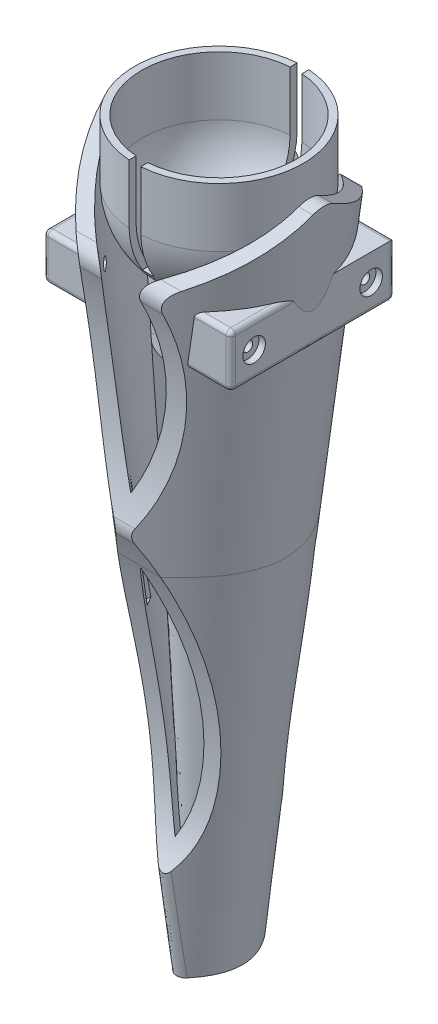
SolidWorks part; units mm, degrees
material "CRPS"
ref_plane "Front Plane" through (0, 0, 0) normal (0, 0, 1) x (1, 0, 0)
ref_plane "Top Plane" through (0, 0, 0) normal (0, 1, 0) x (1, 0, 0)
ref_plane "Right Plane" through (0, 0, 0) normal (1, 0, 0) x (0, 0, -1)
ref_plane "Plane1" through (0, 381, 0) normal (0, 1, 0) x (1, 0, 0)
sketch "Sketch1" plane through (0, 0, 0) normal (0, 1, 0) x (1, 0, 0)
  line L0 (0, 25.4) -> (0, -25.4) construction
  line L1 (-24.0706, 0) -> (20.9677, 0) construction
  ellipse E0 centre (0, 0) end of major axis (0, -25.4) minor radius 12.7 construction
  spline S0 degree 2 poles (0, 25.4) (-25.4, 0) (0, -25.4) knots 0 0 0 1 1 1
  spline S1 degree 2 poles (0, 25.4) (25.4, 0) (0, -25.4) knots 0 0 0 1 1 1
  dimension "D1" = 50.8
  dimension "D2" = 25.4
  dimension "D3" = 25.4
sketch "Sketch2" plane through (0, 381, 0) normal (0, 1, 0) x (1, 0, 0)
  line L0 (0, 76.2) -> (0, -76.2) construction
  line L1 (-84.7486, 0) -> (88.0794, 0) construction
  spline S0 degree 2 poles (0, 76.2) (-114.3, 0) (0, -76.2) knots 0 0 0 1 1 1
  spline S4 degree 2 poles (0, 76.2) (114.3, 0) (0, -76.2) knots 0 0 0 1 1 1
  dimension "D1" = 152.4
loft "Loft1" add profiles "Sketch2", "Sketch1" connector at (0, 381, -76.2) connector at (0, 0, -25.4)
shell "Shell1" thickness 7.62 removed face at (0, 381, 0)
sketch "Sketch3" plane through (0, 0, 0) normal (1, 0, 0) x (0, 0, -1)
  line L0 (0, -10.6087) -> (0, 387.8893) construction
  line L5 (0, 459.1301) -> (-203.7464, 459.1301)
  line L6 (-203.7464, 459.1301) -> (-203.7464, 12.9064)
  line L7 (-203.7464, 12.9064) -> (-69.702, 12.9064)
  line L8 (-69.702, 12.9064) -> (-69.702, 27.0618)
  line L10 (0, 380.3715) -> (0, 459.1301)
  line L11 (-76.2, 381) -> (-25.4, 0) construction
  line L13 (0, 380.3715) -> (-55.9194, 344.4077)
  arc A2 (-55.9194, 344.4077) -> (-52.7686, 223.1491) centre (-207.8896, 279.7886) cw
  spline S0 degree 3 poles (-52.7686, 223.1491) (-29.0646, 178.2411) (18.4946, 46.1783) (-69.702, 27.0618) knots 0 0 0 0 1 1 1 1
extrude "Cut-Extrude3" cut sketch "Sketch3" against normal through all both and the other way through all
mirror "Mirror1" about plane through (0, 0, 0) normal (0, 0, 1) of "Cut-Extrude3"
sketch "Sketch4" plane through (0, 0, 0) normal (0, 0, 1) x (1, 0, 0)
  line L0 (0, 446.903) -> (0, 0) construction
  line L1 (49.405, 380.3715) -> (0, 380.3715) construction
  line L7 (0, 380.3715) -> (0, 393.0715)
  line L8 (0, 393.0715) -> (45.72, 393.0715)
  line L9 (45.72, 393.0715) -> (45.72, 361.0934)
  line L10 (0, 380.3715) -> (0, 316.8715)
  arc A1 (0, 316.8715) -> (45.72, 361.0934) centre (0.1911, 362.4193) ccw
  spline S1 degree 3 poles (20.373, 344.4077) (25.1314, 346.8179) (29.623, 349.3373) (35.8389, 353.3301) (37.8235, 354.6968) (41.5893, 357.5136) (43.3706, 358.9636) (46.6928, 361.9622) (48.2339, 363.5106) (49.9789, 365.5205) (50.3189, 365.9264) (50.9751, 366.7401) (51.9255, 367.9653) (52.7722, 369.2049) (55.3558, 373.3704) (56.661, 376.8089) (57.0767, 380.3715) knots 0 0 0 0 0.25 0.25 0.375 0.375 0.5 0.5 0.625 0.625 0.65625 0.65625 0.6875 0.75 0.75 1 1 1 1 construction
  dimension "D1" = 12.7
  dimension "D2" = 63.5
  dimension "D3" = 45.72
revolve "Revolve1" add sketch "Sketch4" angle 360 about L0
ref_plane "Plane2" through (0, 342.9, 0) normal (0, 1, 0) x (1, 0, 0)
sketch "Sketch7" plane through (0, 342.9, 0) normal (0, 1, 0) x (1, 0, 0)
  circle A0 centre (0, 0) radius 28.575
  dimension "D1" = 57.15
sketch "Sketch9" plane through (0, 7.62, 0) normal (0, 1, 0) x (1, 0, 0)
  circle A1 centre (0, 0) radius 12.7
  dimension "D1" = 25.4
sketch "Sketch11" plane through (0, 0, 0) normal (0, 0, 1) x (1, 0, 0)
  line L0 (0, 0) -> (0, 452.1769) construction
  line L10 (-41.91, 393.0715) -> (-41.91, 361.0934)
  line L11 (45.72, 393.0715) -> (-45.72, 393.0715) construction
  line L12 (45.72, 361.0934) -> (-45.72, 361.0934) construction
  line L13 (0, 319.9717) -> (0, 393.0715)
  line L14 (0, 393.0715) -> (-41.91, 393.0715)
  arc A2 (-41.91, 361.0934) -> (0, 319.9717) centre (0.1848, 362.0776) ccw
  dimension "D1" = 41.91
sketch "Sketch12" plane through (0, 0, 0) normal (1, 0, 0) x (0, 0, -1)
  line L0 (0, 0) -> (0, 403.0292) construction
  line L8 (-4.171, 269.2418) -> (-4.171, 173.919)
  line L10 (-33.8119, 288.677) -> (-25.8319, 168.9729)
  arc A7 (-33.8119, 288.677) -> (-4.171, 269.2418) centre (-28.7091, 264.1389) cw
  arc A8 (-4.171, 173.919) -> (-25.8319, 168.9729) centre (-17.4745, 182.2764) cw
ref_plane "Plane3" through (50.8, 0, 0) normal (1, 0, 0) x (0, 0, -1)
sketch "Sketch13" plane through (50.8, 0, 0) normal (1, 0, 0) x (0, 0, -1)
  line L0 (0, 0) -> (0, 407.2777) construction
  line L2 (-44.45, 338.1582) -> (44.45, 338.1582)
  line L3 (-44.45, 338.1582) -> (-44.45, 309.5418)
  line L4 (-44.45, 309.5418) -> (44.45, 309.5418)
  line L5 (44.45, 338.1582) -> (44.45, 309.5418)
  line L6 (-44.45, 338.1582) -> (44.45, 309.5418) construction
  line L7 (-44.45, 309.5418) -> (44.45, 338.1582) construction
  point P3 (0, 323.85)
  dimension "D1" = 323.85
  dimension "D2" = 88.9
extrude "Boss-Extrude2" add sketch "Sketch13" against normal up to surface (19.3871 mm away) up to face at (20.0933, 168.816, 3.5644)
ref_plane "Plane4" through (-50.8, 0, 0) normal (1, 0, 0) x (0, 0, -1)
sketch "Sketch14" plane through (-50.8, 0, 0) normal (1, 0, 0) x (0, 0, -1)
  line L0 (-23.876, 338.1582) -> (-23.876, 311.423) construction
  line L5 (-44.45, 336.277) -> (44.45, 336.277)
  line L6 (-44.45, 336.277) -> (-44.45, 311.423)
  line L7 (-44.45, 311.423) -> (44.45, 311.423)
  line L8 (44.45, 336.277) -> (44.45, 311.423)
  line L9 (-44.45, 336.277) -> (44.45, 311.423) construction
  line L10 (-44.45, 311.423) -> (44.45, 336.277) construction
  line L11 (-44.45, 338.1582) -> (44.45, 338.1582) construction
  line L12 (-23.876, 323.85) -> (-44.45, 323.85) construction
  line L13 (0, 345.8944) -> (0, 299.4688) construction
  line L14 (0, 0) -> (0, 407.2777) construction
  point P0 (0, 323.85)
  dimension "D1" = 88.9
  dimension "D2" = 323.85
extrude "Boss-Extrude4" add sketch "Sketch14" along normal up to surface (19.6671 mm away) up to face at (-21.1882, 173.8157, -2.0801)
fillet "Fillet2" radius 2.54 17 edges at (38.9583, 309.5418, 44.45) (41.1065, 338.1582, 44.45) (50.8, 323.85, 44.45) (50.8, 338.1582, 27.8992) (50.8, 309.5418, 0) (38.9583, 309.5418, -44.45) (41.1065, 338.1582, -44.45) (50.8, 323.85, -44.45) (-40.9665, 336.277, 44.45) (-39.1008, 311.423, 44.45) (-50.8, 323.85, 44.45) (-50.8, 311.423, 0) (-50.8, 336.277, 27.4106) (-39.1008, 311.423, -44.45) (-50.8, 323.85, -44.45) (-40.9665, 336.277, -44.45) (-50.8, 336.277, -27.4106)
sketch "Sketch28" plane through (0, 0, 0) normal (0, 0, 1) x (1, 0, 0)
  line L0 (0, 0) -> (0, 423.247) construction
  line L7 (-3.175, 414.0584) -> (3.175, 414.0584)
  line L8 (-3.175, 414.0584) -> (-3.175, 337.8584)
  line L9 (-3.175, 337.8584) -> (3.175, 337.8584)
  line L10 (3.175, 414.0584) -> (3.175, 337.8584)
  dimension "D1" = 6.35
  dimension "D2" = 76.2
loft "Loft2" add profiles "Sketch7", "Sketch9" connector at (0, 342.9, 28.575) connector at (0, 7.62, 12.7)
revolve "Cut-Revolve2" cut sketch "Sketch11" angle 360 about L0
extrude "Cut-Extrude6" cut sketch "Sketch12" against normal mid plane 36.83
mirror "Mirror2" about plane through (0, 0, 0) normal (0, 0, 1) of "Cut-Extrude6" second plane through (0, 0, 0) second plane normal (1, 0, 0)
extrude "Cut-Extrude7" cut sketch "Sketch28" against normal through all both and the other way through all
fillet "Fillet3" radius 10 8 edges at (53.2408, 380.3715, 0) (14.3124, 344.4077, 55.9194) (0, 223.1491, 52.7686) (-53.2408, 380.3715, 0) (14.3124, 344.4077, -55.9194) (-14.3124, 344.4077, -55.9194) (0, 223.1491, -52.7686) (-14.3124, 344.4077, 55.9194)
fillet "Fillet4" radius 5.08 2 edges
sketch "Sketch34" plane through (0, 0, 0) normal (0, -1, 0) x (1, 0, 0)
  line L0 (0, 17.78) -> (0, -17.78) construction
  line L1 (-9.0681, 0) -> (7.7305, 0) construction
  point P0 (0, 17.78)
  point P1 (0, -17.78)
  point P9 (0, 17.78)
  point P13 (0, -17.78)
  dimension "D1" = 35.56
hole_wizard "M5 Tapped Hole1" positions "Sketch34" profile "Sketch35" tap size "M5" standard "ISO"
cosmetic thread "Hole Thread1" parameters "D1"=36.83, "D2"=5
cosmetic thread "Hole Thread2" parameters "D1"=36.83, "D2"=5
sketch "Sketch35" plane through (0, 0, -17.78) normal (1, 0, 0) x (0, 0, -1)
  line L0 (0, 0) -> (0, 38.0918)
  line L1 (0, 38.0918) -> (2.1, 36.83)
  line L2 (2.1, 36.83) -> (2.1, 0)
  line L5 (2.1, 0) -> (0, 0)
  line L10 (0, 38.0918) -> (-2.1, 36.83) construction
  line L11 (0, -6.35) -> (0, 107.95) construction
  dimension "Tap Drill Dia." = 4.2
  dimension "Tap Drill Depth" = 36.83
  dimension "Drill Angle" = 118
ref_plane "Plane9" through (0, 279.4, 0) normal (0, 1, 0) x (1, 0, 0)
sketch "Sketch39" plane through (0, 279.4, 0) normal (0, 1, 0) x (1, 0, 0)
  line L0 (0, 17.78) -> (0, -17.78) construction
  line L1 (-12.3506, 0) -> (8.889, 0) construction
  point P0 (0, 17.78)
  point P1 (0, -17.78)
  point P10 (0, -17.78)
  point P12 (0, 17.78)
  dimension "D1" = 35.56
hole_wizard "M5 Tapped Hole3" positions "Sketch39" profile "Sketch40" tap size "M5" standard "ISO" end condition through all
sketch "Sketch40" plane through (0, 279.4, -17.78) normal (1, 0, 0) x (0, 0, -1)
  line L0 (0, 0) -> (0, 113.6715)
  line L1 (0, 113.6715) -> (2.1, 113.6715)
  line L2 (2.1, 113.6715) -> (2.1, 0.425)
  line L3 (2.1, 0.425) -> (2.525, 0)
  line L5 (2.525, 0) -> (0, 0)
  line L6 (-2.1, 0.425) -> (-2.525, 0) construction
  line L11 (0, -6.35) -> (0, 107.95) construction
  dimension "Thru Tap Drill Dia." = 4.2
  dimension "Thru Tap Drill Depth" = 113.6715
  dimension "Near C'Sink Dia." = 5.05
  dimension "Near C'Sink Angle" = 90
cosmetic thread "Hole Thread5" parameters "D2"=5
cosmetic thread "Hole Thread6" parameters "D2"=5
sketch "Sketch41" plane through (50.8, 0, 0) normal (1, 0, 0) x (0, 0, -1)
  line L0 (0, 52.5566) -> (0, 509.4008) construction
  line L1 (-31.75, 323.85) -> (31.75, 323.85) construction
  point P3 (-31.75, 323.85)
  point P4 (31.75, 323.85)
  point P11 (-31.75, 323.85)
  point P15 (31.75, 323.85)
  dimension "D1" = 63.5
hole_wizard "CBORE for M5 Hex Head Bolt1" positions "Sketch41" profile "Sketch44" counterbore size "M5" standard "ISO"
sketch "Sketch44" plane through (50.8, 323.85, -31.75) normal (0, 1, 0) x (0, 0, -1)
  line L0 (0, 0) -> (0, 110.8724)
  line L1 (0, 110.8724) -> (2.75, 109.22)
  line L2 (2.75, 109.22) -> (2.75, 3.5)
  line L3 (2.75, 3.5) -> (6.119, 3.5)
  line L4 (6.119, 3.5) -> (6.119, 0)
  line L5 (6.119, 0) -> (0, 0)
  line L10 (0, 110.8724) -> (-2.75, 109.22) construction
  line L11 (0, -6.35) -> (0, 107.95) construction
  dimension "Hole Dia." = 5.5
  dimension "Hole Depth" = 109.22
  dimension "C'Bore Dia." = 12.238
  dimension "C'Bore Depth" = 3.5
  dimension "Drill Angle" = 118
cosmetic thread "Cosmetic Thread8" parameters "D2"=8
cosmetic thread "Cosmetic Thread9" parameters "D2"=8
cosmetic thread "Cosmetic Thread10" parameters "D2"=8
cosmetic thread "Cosmetic Thread11" parameters "D2"=8
ref_plane "Plane10" through (0, 203.2, 0) normal (0, 1, 0) x (1, 0, 0)
split "Split1" trim tools "Plane10" bodies to split 136 resulting bodies 141 142 143
